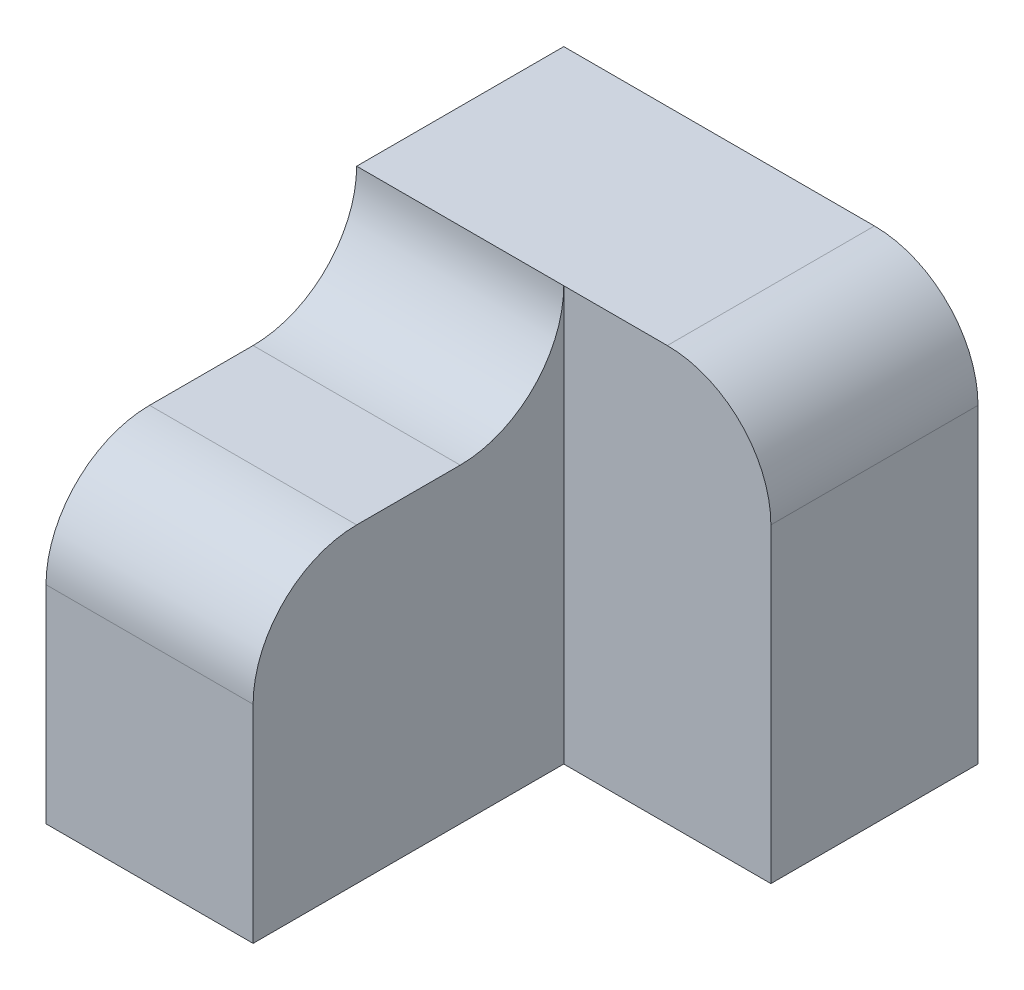
SolidWorks part; units mm, degrees
ref_plane "Front Plane" through (0, 0, 0) normal (0, 0, 1) x (1, 0, 0)
ref_plane "Top Plane" through (0, 0, 0) normal (0, 1, 0) x (1, 0, 0)
ref_plane "Right Plane" through (0, 0, 0) normal (1, 0, 0) x (0, 0, -1)
sketch "Sketch1" plane through (0, 0, 0) normal (0, 0, 1) x (1, 0, 0)
  line L1 (-30, -30) -> (-10, -30)
  line L2 (-10, -30) -> (-10, 0)
  line L3 (-10, 0) -> (-30, 0)
  line L4 (-30, 0) -> (-30, -30)
  dimension "D1" = 20
  dimension "Width" = 30
extrude "Boss-Extrude1" add sketch "Sketch1" along normal blind 30
sketch "Sketch2" plane through (0, 0, 0) normal (0, 0, 1) x (1, 0, 0)
  line L1 (-30, -30) -> (10, -30)
  line L2 (10, -30) -> (10, 10)
  line L3 (10, 10) -> (-30, 10)
  line L4 (-30, 10) -> (-30, -30)
  dimension "D1" = 40
  dimension "Width" = 40
extrude "Boss-Extrude2" add sketch "Sketch2" against normal blind 20
fillet "Fillet1" radius 10 3 edges at (-20, 0, 0) (10, 10, -10) (-20, 0, 30)
